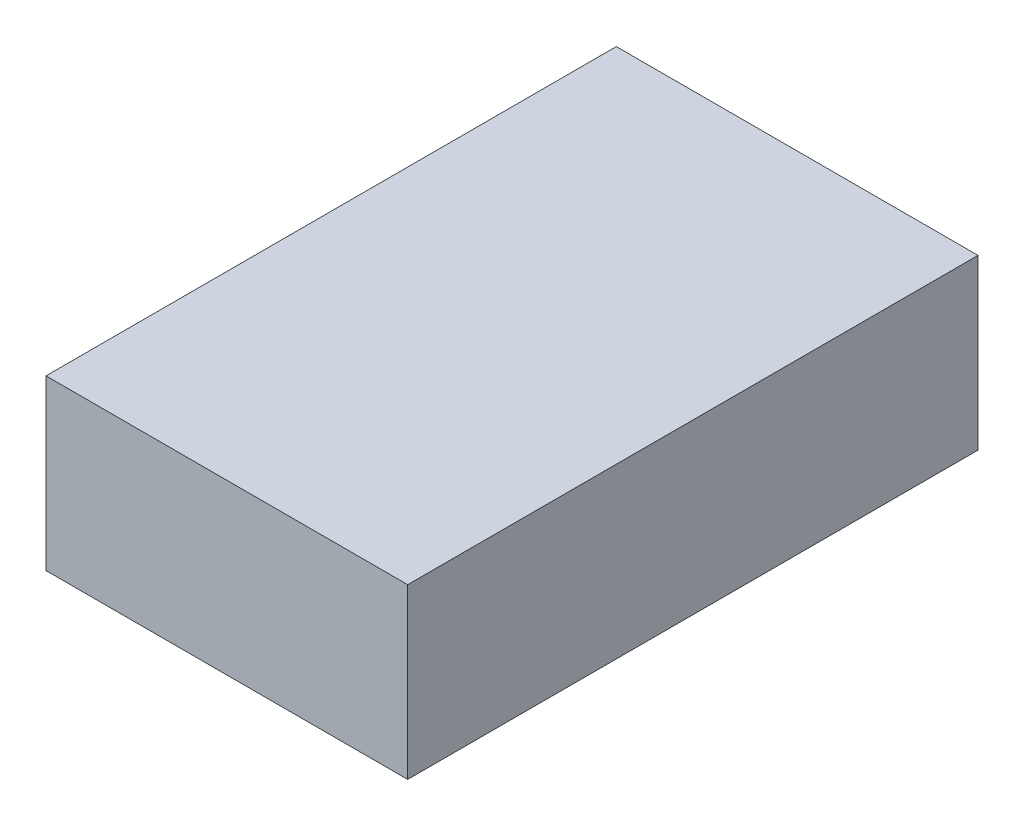
SolidWorks part; units mm, degrees
ref_plane "Front Plane" through (0, 0, 0) normal (0, 0, 1) x (1, 0, 0)
ref_plane "Top Plane" through (0, 0, 0) normal (0, 1, 0) x (1, 0, 0)
ref_plane "Right Plane" through (0, 0, 0) normal (1, 0, 0) x (0, 0, -1)
sketch "Sketch1" plane through (0, 0, 0) normal (0, 1, 0) x (1, 0, 0)
  line L1 (-33.02, -52.07) -> (33.02, -52.07)
  line L2 (-33.02, -52.07) -> (-33.02, 52.07)
  line L3 (-33.02, 52.07) -> (33.02, 52.07)
  line L4 (33.02, -52.07) -> (33.02, 52.07)
  line L5 (-33.02, -52.07) -> (33.02, 52.07) construction
  line L6 (-33.02, 52.07) -> (33.02, -52.07) construction
  point P0 (0, 0)
  dimension "D1" = 66.04
  dimension "D2" = 104.14
extrude "Boss-Extrude1" add sketch "Sketch1" along normal blind 30.7975
